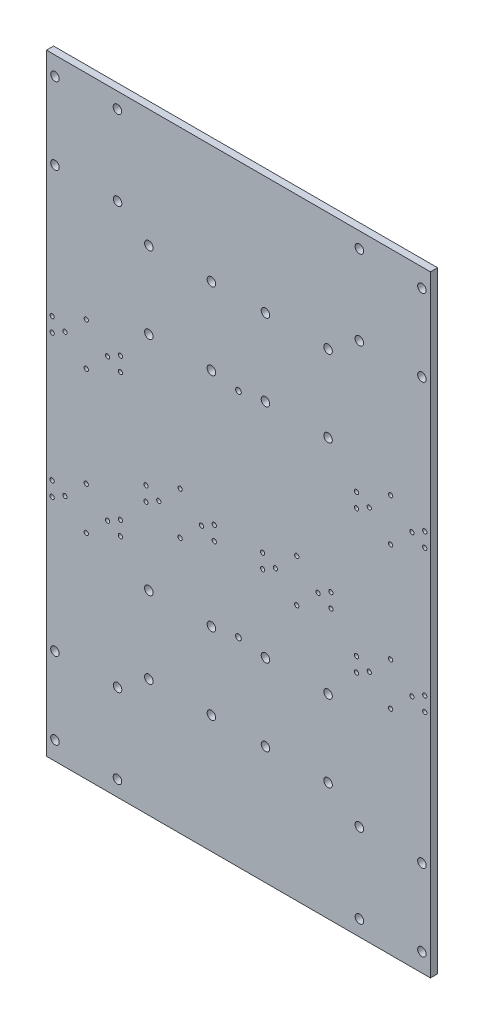
SolidWorks part; units mm, degrees
material "铜"
ref_plane "前视基准面" through (0, 0, 0) normal (0, 0, 1) x (1, 0, 0)
ref_plane "上视基准面" through (0, 0, 0) normal (0, 1, 0) x (1, 0, 0)
ref_plane "右视基准面" through (0, 0, 0) normal (1, 0, 0) x (0, 0, -1)
sketch "草图1" plane through (0, 0, 0) normal (0, 0, 1) x (1, 0, 0)
  line L1 (-135, -215) -> (135, -215)
  line L2 (-135, -215) -> (-135, 215)
  line L3 (-135, 215) -> (135, 215)
  line L4 (135, -215) -> (135, 215)
  line L5 (-135, -215) -> (135, 215) construction
  line L6 (-135, 215) -> (135, -215) construction
  point P0 (0, 0)
  dimension "D1" = 270
  dimension "D2" = 430
base flange "、" sketch "草图1" thickness 5 reverse thickness direction no parameters "D1"=0.7366
sketch "草图6" plane through (0, 0, 0) normal (0, 0, 1) x (1, 0, 0)
  line L0 (135, 215) -> (-135, 215) construction
  line L1 (-125, -170) -> (125, -170) construction
  line L2 (-125, -170) -> (-125, 170) construction
  line L3 (-125, 170) -> (125, 170) construction
  line L4 (125, -170) -> (125, 170) construction
  line L5 (-125, -170) -> (125, 170) construction
  line L6 (-125, 170) -> (125, -170) construction
  line L7 (-135, 215) -> (-135, -215) construction
  circle A0 centre (-105, 185) radius 2
  circle A1 centre (-120, 170) radius 2
  circle A2 centre (-90, 170) radius 2
  circle A3 centre (-105, 155) radius 2
  point P1 (0, 0)
  dimension "D3" = 4
  dimension "D4" = 4
  dimension "D5" = 4
  dimension "D6" = 4
  dimension "D1" = 45
  dimension "D2" = 10
  dimension "D7" = 15
  dimension "D8" = 15
  dimension "D9" = 15
  dimension "D10" = 20
  dimension "D11" = 20
  dimension "D12" = 15
extrude "切除-拉伸1" [suppressed] cut sketch "草图6" against normal blind 10
mirror "镜向1" [suppressed] about plane through (0, 0, 0) normal (1, 0, 0)
mirror "镜向2" [suppressed] about plane through (0, 0, 0) normal (0, 1, 0)
sketch "草图7" plane through (0, 0, 0) normal (0, 0, 1) x (1, 0, 0)
  line L0 (-135, 0) -> (135, 0) construction
  line L1 (-135, 215) -> (-135, -215) construction
  line L2 (135, -215) -> (135, 215) construction
  line L3 (0, 215) -> (0, -215) construction
  line L4 (135, 215) -> (-135, 215) construction
  line L5 (-135, -215) -> (135, -215) construction
  circle A0 centre (125, 0) radius 2
  circle A1 centre (125, 70) radius 2
  circle A2 centre (125, -70) radius 2
  dimension "D1" = 4
  dimension "D3" = 4
  dimension "D4" = 4
  dimension "D2" = 10
  dimension "D5" = 10
  dimension "D6" = 70
  dimension "D7" = 10
  dimension "D8" = 70
extrude "切除-拉伸2" [suppressed] cut sketch "草图7" against normal blind 10
pattern_circular "阵列(圆周)1" [suppressed] count 4 over 360
sketch "草图8" plane through (0, 0, 0) normal (0, 0, 1) x (1, 0, 0)
  line L0 (-135, 0) -> (135, 0) construction
  line L1 (-135, 215) -> (-135, -215) construction
  line L2 (135, -215) -> (135, 215) construction
  line L3 (0, 215) -> (0, -215) construction
  line L4 (135, 215) -> (-135, 215) construction
  line L5 (-135, -215) -> (135, -215) construction
  line L7 (-85, -25) -> (-35, -25) construction
  line L8 (-85, -25) -> (-85, 25) construction
  line L9 (-85, 25) -> (-35, 25) construction
  line L10 (-35, -25) -> (-35, 25) construction
  line L11 (-85, -25) -> (-35, 25) construction
  line L12 (-85, 25) -> (-35, -25) construction
  line L13 (27.3523, -33.714) -> (92.6477, -33.714) construction
  line L14 (27.3523, -33.714) -> (27.3523, 33.714) construction
  line L15 (27.3523, 33.714) -> (92.6477, 33.714) construction
  line L16 (92.6477, -33.714) -> (92.6477, 33.714) construction
  line L17 (27.3523, -33.714) -> (92.6477, 33.714) construction
  line L18 (27.3523, 33.714) -> (92.6477, -33.714) construction
  circle A0 centre (60, 0) radius 27.5
  circle A1 centre (-60, 0) radius 27.5
  circle A2 centre (-60, 0) radius 35.355 construction
  circle A3 centre (-84.9998, 24.9998) radius 2
  circle A4 centre (-35.0002, 24.9998) radius 2
  circle A5 centre (-35.0002, -24.9998) radius 2
  circle A6 centre (-84.9998, -24.9998) radius 2
  circle A7 centre (35.0002, -24.9998) radius 2
  circle A8 centre (84.9998, -24.9998) radius 2
  circle A9 centre (35.0002, 24.9998) radius 2
  circle A10 centre (84.9998, 24.9998) radius 2
  point P37 (-60, 0)
  dimension "D1" = 55
  dimension "D2" = 55
  dimension "D7" = 70.71
  dimension "D8" = 4
  dimension "D3" = 60
  dimension "D4" = 60
  dimension "D5" = 50
  dimension "D6" = 50
  dimension "D9" = 4
extrude "切除-拉伸3" [suppressed] cut sketch "草图8" against normal blind 10
sketch "草图9" plane through (0, 0, 0) normal (0, 0, 1) x (1, 0, 0)
  line L0 (0, 215) -> (0, -215) construction
  line L1 (135, 215) -> (-135, 215) construction
  line L2 (-135, -215) -> (135, -215) construction
  circle A0 centre (0, 75) radius 2
  circle A1 centre (0, -75) radius 2
  dimension "D1" = 4
  dimension "D4" = 4
  dimension "D2" = 75
  dimension "D3" = 75
extrude "切除-拉伸4" cut sketch "草图9" against normal blind 10 normal cut yes
sketch "草图10" plane through (0, 0, 0) normal (0, 0, 1) x (1, 0, 0)
  line L0 (135, 215) -> (-135, 215) construction
  line L1 (-135, 215) -> (-135, -215) construction
  circle A0 centre (-107, 50) radius 15 construction
  circle A1 centre (-107, 65) radius 1.5
  circle A2 centre (-92, 50) radius 1.5
  circle A3 centre (-107, 35) radius 1.5
  circle A4 centre (-122, 50) radius 1.5
  point P17 (-107, 50)
  dimension "D3" = 30
  dimension "D4" = 3
  dimension "D1" = 165
  dimension "D2" = 28
  dimension "D5" = 4
extrude "切除-拉伸5" cut sketch "草图10" against normal blind 10 normal cut yes
sketch "草图11" plane through (0, 0, -5) normal (0, 0, -1) x (-1, 0, 0)
  line L0 (135, 215) -> (135, -215) construction
  line L1 (107, 63.5) -> (107, 36.5) construction
  circle A0 centre (131, 55) radius 1.5
  circle A1 centre (131, 45) radius 1.5
  circle A2 centre (122, 50) radius 1.5 construction
  circle A3 centre (107, 65) radius 1.5 construction
  circle A4 centre (107, 35) radius 1.5 construction
  circle A5 centre (83, 45) radius 1.5
  circle A6 centre (83, 55) radius 1.5
  dimension "D1" = 3
  dimension "D2" = 3
  dimension "D3" = 4
  dimension "D4" = 4
  dimension "D5" = 5
  dimension "D6" = 10
extrude "切除-拉伸6" cut sketch "草图11" against normal blind 10 normal cut yes
mirror "镜向3" about plane through (0, 0, 0) normal (1, 0, 0) of "切除-拉伸6", "切除-拉伸5"
mirror "镜向4" about plane through (0, 0, 0) normal (0, 1, 0) of "镜向3", "切除-拉伸5", "切除-拉伸6"
sketch "草图12" plane through (0, 0, -5) normal (0, 0, -1) x (-1, 0, 0)
  line L0 (-135, 215) -> (135, 215) construction
  line L1 (-135, -215) -> (-135, 215) construction
  circle A0 centre (-129, 202) radius 3
  circle A1 centre (-129, 148) radius 3
  circle A2 centre (-85.0455, 204) radius 3
  circle A3 centre (-85, 148) radius 3
  dimension "D2" = 6
  dimension "D6" = 6
  dimension "D7" = 6
  dimension "D8" = 6
  dimension "D10" = 0
  dimension "D1" = 13
  dimension "D3" = 6
  dimension "D4" = 6
  dimension "D5" = 54
  dimension "D9" = 44
  dimension "D11" = 56
  dimension "D12" = 44
extrude "切除-拉伸7" cut sketch "草图12" against normal blind 10 normal cut yes
mirror "镜向5" about plane through (0, 0, 0) normal (0, 1, 0) of "切除-拉伸7"
mirror "镜向6" about plane through (0, 0, 0) normal (1, 0, 0) of "镜向5", "切除-拉伸7"
sketch "草图13" plane through (0, 0, -5) normal (0, 0, -1) x (-1, 0, 0)
  line L1 (-85, -148) -> (-63, -148) construction
  line L2 (-85, -148) -> (-85, -132) construction
  line L3 (-85, -132) -> (-63, -132) construction
  line L4 (-63, -148) -> (-63, -132) construction
  circle A0 centre (-63, -132) radius 3
  circle A1 centre (-63, -78) radius 3
  circle A2 centre (-19, -78) radius 3
  circle A3 centre (-19, -132) radius 3
  dimension "D3" = 6
  dimension "D4" = 6
  dimension "D5" = 6
  dimension "D6" = 6
  dimension "D1" = 22
  dimension "D2" = 16
  dimension "D7" = 44
  dimension "D8" = 54
  dimension "D9" = 44
  dimension "D10" = 54
extrude "切除-拉伸8" cut sketch "草图13" against normal blind 10 normal cut yes
mirror "镜向7" about plane through (0, 0, 0) normal (1, 0, 0) of "切除-拉伸8"
mirror "镜向8" about plane through (0, 0, 0) normal (0, 1, 0) of "镜向7", "切除-拉伸8"
sketch "草图14" plane through (0, 0, -5) normal (0, 0, -1) x (-1, 0, 0)
  line L0 (-63, 132) -> (-19, 132) construction
  line L1 (-41, 132) -> (-41, -20) construction
  circle A0 centre (-41, -20) radius 15 construction
  circle A1 centre (-41, -5) radius 1.5
  circle A2 centre (-26, -20) radius 1.5
  circle A3 centre (-41, -35) radius 1.5
  circle A4 centre (-56, -20) radius 1.5
  circle A5 centre (-65.005, -15) radius 1.5
  circle A6 centre (-65.005, -25) radius 1.5
  circle A7 centre (-16.995, -25) radius 1.5
  circle A8 centre (-16.995, -15) radius 1.5
  point P18 (-41, -20)
  dimension "D2" = 30
  dimension "D3" = 3
  dimension "D5" = 3
  dimension "D6" = 3
  dimension "D1" = 152
  dimension "D7" = 5
  dimension "D8" = 10
  dimension "D9" = 10.3
  dimension "D10" = 10.3
  dimension "D4" = 4
extrude "切除-拉伸9" cut sketch "草图14" against normal blind 10 normal cut yes
mirror "镜向9" about plane through (0, 0, 0) normal (1, 0, 0) of "切除-拉伸9"
sketch "折弯-线1" [suppressed] plane through (0, 0, 0) normal (0, 1, 0) x (1, 0, 0)
sketch "边界框1" [suppressed] plane through (0, 0, 0) normal (0, 1, 0) x (1, 0, 0)
sheet metal parameters "钣金1" thickness 5 parameters "D1"=0.7366
flat pattern "平板型式1" [suppressed]
sketch "折弯-线2" plane through (0, 0, 0) normal (0, 1, 0) x (1, 0, 0)
sketch3d "边界框2" [suppressed]
  line L0 (-150, 200, 0) -> (-150, -200, 0) construction
  line L1 (150, 200, 0) -> (150, -200, 0) construction
  line L2 (-150, 200, 0) -> (150, 200, 0) construction
  line L3 (-150, -200, 0) -> (150, -200, 0) construction
sheet metal parameters "钣金2" thickness 5 parameters "D1"=0.7366
flat pattern "平板型式1"
sketch "折弯-线2" plane through (0, 0, 0) normal (0, 1, 0) x (1, 0, 0)
sketch3d "边界框2" [suppressed]
  line L0 (150, 200, 0) -> (150, -200, 0) construction
  line L1 (-150, 200, 0) -> (-150, -200, 0) construction
  line L2 (150, 200, 0) -> (-150, 200, 0) construction
  line L3 (150, -200, 0) -> (-150, -200, 0) construction
sheet metal parameters "钣金3" thickness 5 parameters "D1"=0.7366
flat pattern "平板型式1"
sketch "折弯-线2" plane through (0, 0, 0) normal (0, 1, 0) x (1, 0, 0)
sketch3d "边界框2" [suppressed]
  line L0 (150, 200, 0) -> (150, -200, 0) construction
  line L1 (-150, 200, 0) -> (-150, -200, 0) construction
  line L2 (150, 200, 0) -> (-150, 200, 0) construction
  line L3 (150, -200, 0) -> (-150, -200, 0) construction
sheet metal parameters "钣金4" thickness 5 parameters "D1"=0.7366
flat pattern "平板型式1"
sketch "折弯-线2" plane through (0, 0, 0) normal (0, 1, 0) x (1, 0, 0)
sketch3d "边界框2" [suppressed]
  line L0 (150, 200, 0) -> (150, -200, 0) construction
  line L1 (-150, 200, 0) -> (-150, -200, 0) construction
  line L2 (150, 200, 0) -> (-150, 200, 0) construction
  line L3 (150, -200, 0) -> (-150, -200, 0) construction
sheet metal parameters "钣金5" thickness 5 parameters "D1"=0.7366
flat pattern "平板型式1"
sketch "折弯-线2" plane through (0, 0, 0) normal (0, 1, 0) x (1, 0, 0)
sketch3d "边界框2" [suppressed]
  line L0 (150, 200, 0) -> (150, -200, 0) construction
  line L1 (-150, 200, 0) -> (-150, -200, 0) construction
  line L2 (150, 200, 0) -> (-150, 200, 0) construction
  line L3 (150, -200, 0) -> (-150, -200, 0) construction
sheet metal parameters "钣金6" thickness 5 parameters "D1"=0.7366
flat pattern "平板型式1"
sketch "折弯-线2" plane through (0, 0, 0) normal (0, 1, 0) x (1, 0, 0)
sketch3d "边界框2" [suppressed]
  line L0 (150, 200, 0) -> (150, -200, 0) construction
  line L1 (-150, 200, 0) -> (-150, -200, 0) construction
  line L2 (150, 200, 0) -> (-150, 200, 0) construction
  line L3 (150, -200, 0) -> (-150, -200, 0) construction
sheet metal parameters "钣金7" thickness 5 parameters "D1"=0.7366
flat pattern "平板型式1"
sketch "折弯-线2" plane through (0, 0, 0) normal (0, 1, 0) x (1, 0, 0)
sketch3d "边界框2" [suppressed]
  line L0 (150, 200, 0) -> (150, -200, 0) construction
  line L1 (-150, 200, 0) -> (-150, -200, 0) construction
  line L2 (150, 200, 0) -> (-150, 200, 0) construction
  line L3 (150, -200, 0) -> (-150, -200, 0) construction
sheet metal parameters "钣金8" thickness 5 parameters "D1"=0.7366
flat pattern "平板型式1"
sketch "折弯-线2" plane through (0, 0, 0) normal (0, 1, 0) x (1, 0, 0)
sketch3d "边界框2" [suppressed]
  line L0 (150, 225, 0) -> (150, -225, 0) construction
  line L1 (-150, 225, 0) -> (-150, -225, 0) construction
  line L2 (150, 225, 0) -> (-150, 225, 0) construction
  line L3 (150, -225, 0) -> (-150, -225, 0) construction
sheet metal parameters "钣金9" thickness 5 parameters "D1"=0.7366
flat pattern "平板型式1"
sketch "折弯-线2" plane through (0, 0, 0) normal (0, 1, 0) x (1, 0, 0)
sketch3d "边界框2" [suppressed]
  line L0 (150, 225, 0) -> (150, -225, 0) construction
  line L1 (-150, 225, 0) -> (-150, -225, 0) construction
  line L2 (150, 225, 0) -> (-150, 225, 0) construction
  line L3 (150, -225, 0) -> (-150, -225, 0) construction
sheet metal parameters "钣金10" thickness 5 parameters "D1"=0.7366
flat pattern "平板型式1"
sketch "折弯-线2" plane through (0, 0, 0) normal (0, 1, 0) x (1, 0, 0)
sketch3d "边界框2" [suppressed]
  line L0 (150, 225, 0) -> (150, -225, 0) construction
  line L1 (-150, 225, 0) -> (-150, -225, 0) construction
  line L2 (150, 225, 0) -> (-150, 225, 0) construction
  line L3 (150, -225, 0) -> (-150, -225, 0) construction
sheet metal parameters "钣金11" thickness 5 parameters "D1"=0.7366
flat pattern "平板型式1"
sketch "折弯-线2" plane through (0, 0, 0) normal (0, 1, 0) x (1, 0, 0)
sketch3d "边界框2" [suppressed]
  line L0 (150, 225, 0) -> (150, -225, 0) construction
  line L1 (-150, 225, 0) -> (-150, -225, 0) construction
  line L2 (150, 225, 0) -> (-150, 225, 0) construction
  line L3 (150, -225, 0) -> (-150, -225, 0) construction
sheet metal parameters "钣金12" thickness 5 parameters "D1"=0.7366
flat pattern "平板型式1"
sketch "折弯-线2" plane through (0, 0, 0) normal (0, 1, 0) x (1, 0, 0)
sketch3d "边界框2" [suppressed]
  line L0 (150, 225, 0) -> (150, -225, 0) construction
  line L1 (-150, 225, 0) -> (-150, -225, 0) construction
  line L2 (150, 225, 0) -> (-150, 225, 0) construction
  line L3 (150, -225, 0) -> (-150, -225, 0) construction
sheet metal parameters "钣金13" thickness 5 parameters "D1"=0.7366
flat pattern "平板型式1"
sketch "折弯-线2" plane through (0, 0, 0) normal (0, 1, 0) x (1, 0, 0)
sketch3d "边界框2" [suppressed]
  line L0 (150, 225, 0) -> (150, -225, 0) construction
  line L1 (-150, 225, 0) -> (-150, -225, 0) construction
  line L2 (150, 225, 0) -> (-150, 225, 0) construction
  line L3 (150, -225, 0) -> (-150, -225, 0) construction
sheet metal parameters "钣金14" thickness 5 parameters "D1"=0.7366
flat pattern "平板型式1"
sketch "折弯-线2" plane through (0, 0, 0) normal (0, 1, 0) x (1, 0, 0)
sketch3d "边界框2" [suppressed]
  line L0 (150, 225, 0) -> (150, -225, 0) construction
  line L1 (-150, 225, 0) -> (-150, -225, 0) construction
  line L2 (150, 225, 0) -> (-150, 225, 0) construction
  line L3 (150, -225, 0) -> (-150, -225, 0) construction
sheet metal parameters "钣金15" thickness 5 parameters "D1"=0.7366
flat pattern "平板型式1"
sketch "折弯-线2" plane through (0, 0, 0) normal (0, 1, 0) x (1, 0, 0)
sketch3d "边界框2" [suppressed]
  line L0 (150, 225, 0) -> (150, -225, 0) construction
  line L1 (-150, 225, 0) -> (-150, -225, 0) construction
  line L2 (150, 225, 0) -> (-150, 225, 0) construction
  line L3 (150, -225, 0) -> (-150, -225, 0) construction
sheet metal parameters "钣金16" thickness 5 parameters "D1"=0.7366
flat pattern "平板型式1"
sketch "折弯-线2" plane through (0, 0, 0) normal (0, 1, 0) x (1, 0, 0)
sketch3d "边界框2" [suppressed]
  line L0 (150, 225, 0) -> (150, -225, 0) construction
  line L1 (-150, 225, 0) -> (-150, -225, 0) construction
  line L2 (150, 225, 0) -> (-150, 225, 0) construction
  line L3 (150, -225, 0) -> (-150, -225, 0) construction
sheet metal parameters "钣金17" thickness 5 parameters "D1"=0.7366
flat pattern "平板型式1"
sketch "折弯-线2" plane through (0, 0, 0) normal (0, 1, 0) x (1, 0, 0)
sketch3d "边界框2" [suppressed]
  line L0 (150, 225, 0) -> (150, -225, 0) construction
  line L1 (-150, 225, 0) -> (-150, -225, 0) construction
  line L2 (150, 225, 0) -> (-150, 225, 0) construction
  line L3 (150, -225, 0) -> (-150, -225, 0) construction
sheet metal parameters "钣金18" thickness 5 parameters "D1"=0.7366
flat pattern "平板型式1"
sketch "折弯-线2" plane through (0, 0, 0) normal (0, 1, 0) x (1, 0, 0)
sketch3d "边界框2" [suppressed]
  line L0 (150, 225, 0) -> (150, -225, 0) construction
  line L1 (-150, 225, 0) -> (-150, -225, 0) construction
  line L2 (150, 225, 0) -> (-150, 225, 0) construction
  line L3 (150, -225, 0) -> (-150, -225, 0) construction
sheet metal parameters "钣金19" thickness 5 parameters "D1"=0.7366
flat pattern "平板型式1"
sketch "折弯-线2" plane through (0, 0, 0) normal (0, 1, 0) x (1, 0, 0)
sketch3d "边界框2" [suppressed]
  line L0 (150, 225, 0) -> (150, -225, 0) construction
  line L1 (-150, 225, 0) -> (-150, -225, 0) construction
  line L2 (150, 225, 0) -> (-150, 225, 0) construction
  line L3 (150, -225, 0) -> (-150, -225, 0) construction
sheet metal parameters "钣金20" thickness 5 parameters "D1"=0.7366
flat pattern "平板型式1"
sketch "折弯-线2" plane through (0, 0, 0) normal (0, 1, 0) x (1, 0, 0)
sketch3d "边界框2" [suppressed]
  line L0 (135, 215, 0) -> (135, -215, 0) construction
  line L1 (-135, 215, 0) -> (-135, -215, 0) construction
  line L2 (135, 215, 0) -> (-135, 215, 0) construction
  line L3 (135, -215, 0) -> (-135, -215, 0) construction
